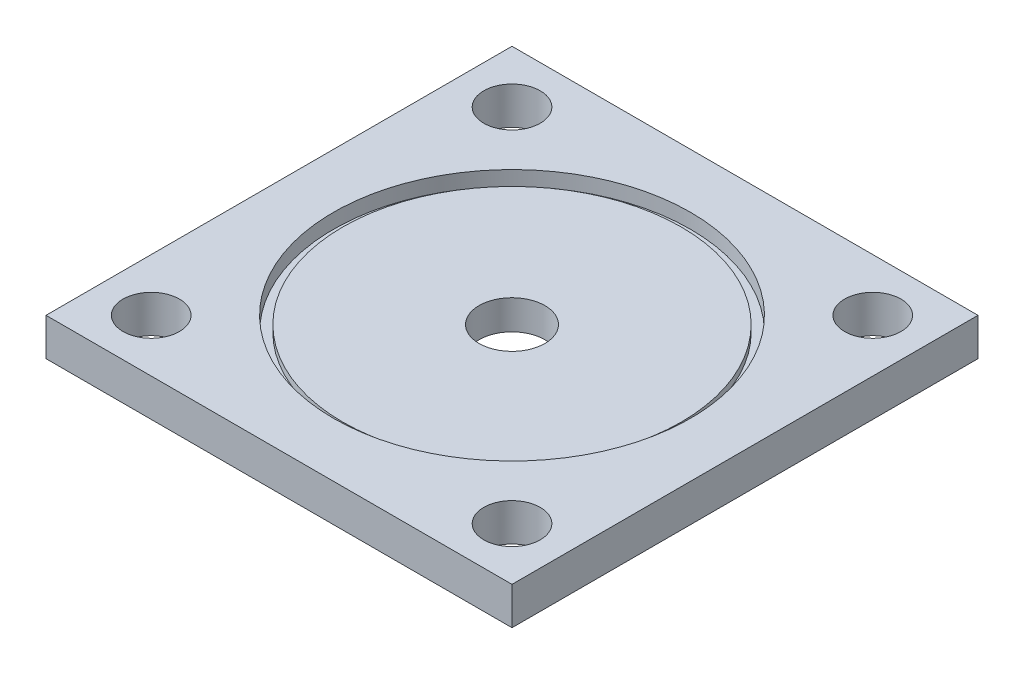
SolidWorks part; units mm, degrees
ref_plane "Front Plane" through (0, 0, 0) normal (0, 0, 1) x (1, 0, 0)
ref_plane "Top Plane" through (0, 0, 0) normal (0, 1, 0) x (1, 0, 0)
ref_plane "Right Plane" through (0, 0, 0) normal (1, 0, 0) x (0, 0, -1)
sketch "plateOutline" plane through (0, 0, 0) normal (0, 1, 0) x (1, 0, 0)
  line L1 (-39.37, -39.37) -> (39.37, -39.37)
  line L2 (-39.37, -39.37) -> (-39.37, 39.37)
  line L3 (-39.37, 39.37) -> (39.37, 39.37)
  line L4 (39.37, -39.37) -> (39.37, 39.37)
  line L5 (-39.37, -39.37) -> (39.37, 39.37) construction
  line L6 (-39.37, 39.37) -> (39.37, -39.37) construction
  line L7 (-39.37, -39.37) -> (39.37, -39.37) construction
  line L8 (-39.37, -39.37) -> (-39.37, 39.37) construction
  line L9 (-39.37, 39.37) -> (39.37, 39.37) construction
  line L10 (39.37, -39.37) -> (39.37, 39.37) construction
  point P0 (0, 0)
  dimension "D1" = 78.74
sketch "railGuides" plane through (0, 0, 0) normal (0, 1, 0) x (1, 0, 0)
  line L0 (-30.48, 30.48) -> (30.48, 30.48) construction
  line L1 (30.48, -30.48) -> (30.48, 30.48) construction
  line L2 (-30.48, -30.48) -> (30.48, -30.48) construction
  line L3 (-30.48, -30.48) -> (-30.48, 30.48) construction
  line L5 (-40.005, -40.005) -> (40.005, -40.005) construction
  line L11 (-40.005, -40.005) -> (-40.005, 40.005) construction
  line L12 (-40.005, 40.005) -> (40.005, 40.005) construction
  line L13 (40.005, -40.005) -> (40.005, 40.005) construction
  line L14 (-40.005, -40.005) -> (40.005, 40.005) construction
  line L15 (-40.005, 40.005) -> (40.005, -40.005) construction
  circle A0 centre (-30.48, 30.48) radius 4.7625
  circle A1 centre (30.48, 30.48) radius 4.7625
  circle A2 centre (30.48, -30.48) radius 4.7625
  circle A3 centre (-30.48, -30.48) radius 4.7625
  point P1 (0, 0)
  dimension "D1" = 80.01
  dimension "D3" = 9.525
  dimension "D4" = 9.525
  dimension "D5" = 9.525
  dimension "D6" = 9.525
  dimension "D7" = 9.525
  dimension "D2" = 80.01
sketch "FuelGrainMounting" plane through (0, 0, 0) normal (0, 1, 0) x (1, 0, 0)
  circle A0 centre (0, 0) radius 30.1625
  dimension "D1" = 60.325
sketch "GasIntake" plane through (0, 0, 0) normal (0, 1, 0) x (1, 0, 0)
  line L0 (-39.37, 39.37) -> (39.37, -39.37) construction
  circle A0 centre (0, 0) radius 5.5562
  dimension "D1" = 11.1125
extrude "Boss-Extrude1" add sketch "plateOutline" along normal blind 6.35 contours L3 L4 L1 L2
extrude "Cut-Extrude1" cut sketch "railGuides" along normal blind 10 contours A0 | A3 | A1 | A2 region at (-30.48, 0, -30.48)
extrude "Cut-Extrude2" cut sketch "FuelGrainMounting" along normal blind 5 from offset 5
extrude "Cut-Extrude3" cut sketch "GasIntake" along normal blind 5
sketch "Sketch1" plane through (0, 0, 0) normal (0, 1, 0) x (1, 0, 0)
  circle A0 centre (0, 0) radius 28.575
  circle A2 centre (0, 0) radius 30.1625
  dimension "D1" = 60.325
  dimension "D2" = 57.15
extrude "Cut-Extrude4" cut sketch "Sketch1" against normal blind 1.143 from offset 5
